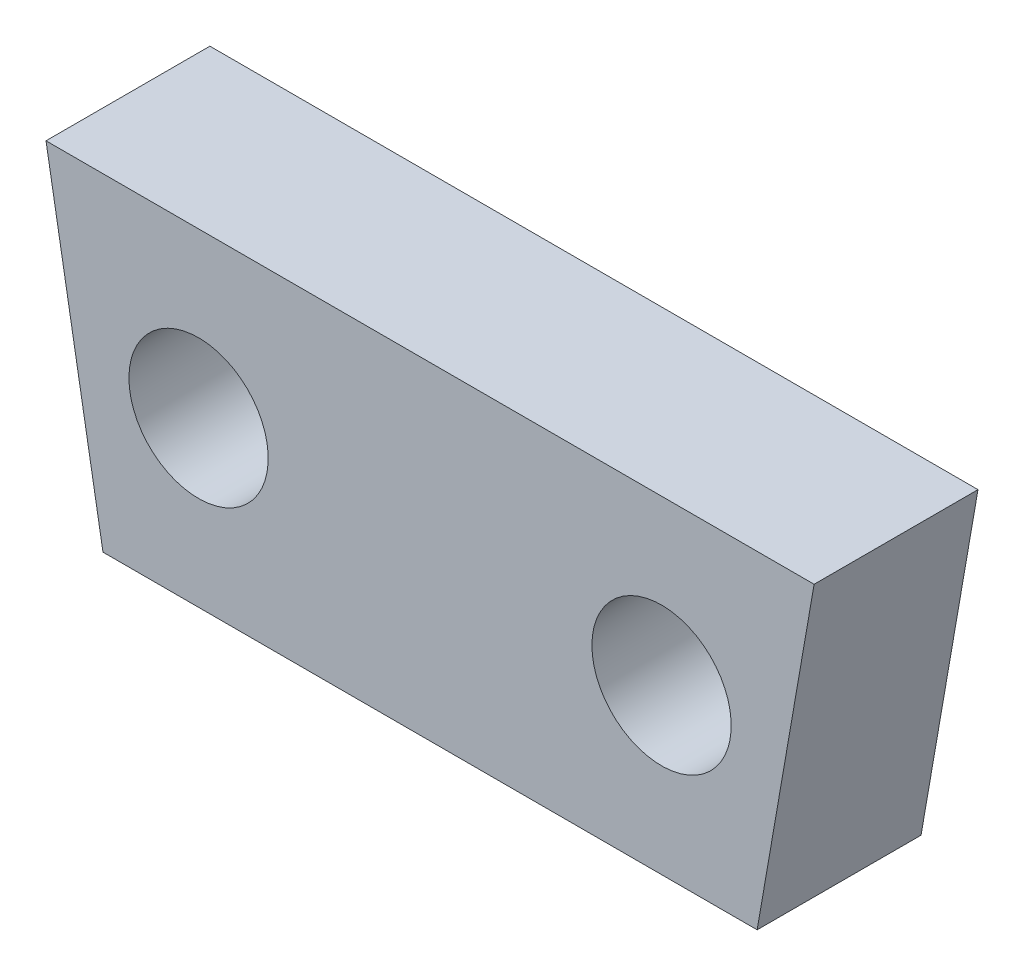
SolidWorks part; units mm, degrees
material "PLA Black"
ref_plane "Front" through (0, 0, 0) normal (0, 0, 1) x (1, 0, 0)
ref_plane "Top" through (0, 0, 0) normal (0, 1, 0) x (1, 0, 0)
ref_plane "Right" through (0, 0, 0) normal (1, 0, 0) x (0, 0, -1)
sketch "Sketch1" plane through (0, 0, 0) normal (0, 0, -1) x (1, 0, 0)
  line L0 (7.9832, 4) -> (-7.9832, 4)
  line L1 (-9.3736, -4) -> (9.3736, -4)
  line L2 (9.3736, -4) -> (7.9832, 4)
  line L3 (-9.3736, -4) -> (-7.9832, 4)
  line L4 (0, 8.8039) -> (0, -5.128) construction
  line L5 (-9.3736, -4) -> (9.3736, -4) construction
  line L6 (10.8682, 0) -> (-14.6589, 0) construction
  spline S0 degree 3 poles (9.3736, -4) (8.9651, -2.0165) (8.5981, -0.0242) (7.9684, 3.977) (7.7062, 5.9847) (7.5, 8) knots 0 0 0 0 0.5 0.5 1 1 1 1 construction
  spline S3 degree 3 poles (-7.5, 8) (-7.7062, 5.9847) (-7.9684, 3.977) (-8.5981, -0.0242) (-8.9651, -2.0165) (-9.3736, -4) knots 0 0 0 0 0.5 0.5 1 1 1 1 construction
extrude "Boss-Extrude1" add sketch "Sketch1" along normal blind 4
hole_wizard "M3 Clearance Hole1" positions "Sketch4" profile "Sketch3" hole size "M3" standard "DIN" end condition through all
sketch "Sketch4" plane through (0, 0, -4) normal (0, 0, -1) x (-1, 0, 0)
  circle A1 centre (-5.65, 0) radius 2.15 construction
  circle A2 centre (5.65, 0) radius 2.15 construction
  point P0 (-5.65, 0)
  point P2 (5.65, 0)
sketch "Sketch3" plane through (5.65, 0, -4) normal (1, 0, 0) x (0, 1, 0)
  line L0 (0, 0) -> (0, 4)
  line L1 (0, 4) -> (1.7, 4)
  line L2 (1.7, 4) -> (1.7, 0)
  line L5 (1.7, 0) -> (0, 0)
  line L11 (0, -6.35) -> (0, 107.95) construction
  dimension "Thru Hole Dia." = 3.4
  dimension "Thru Hole Depth" = 4
